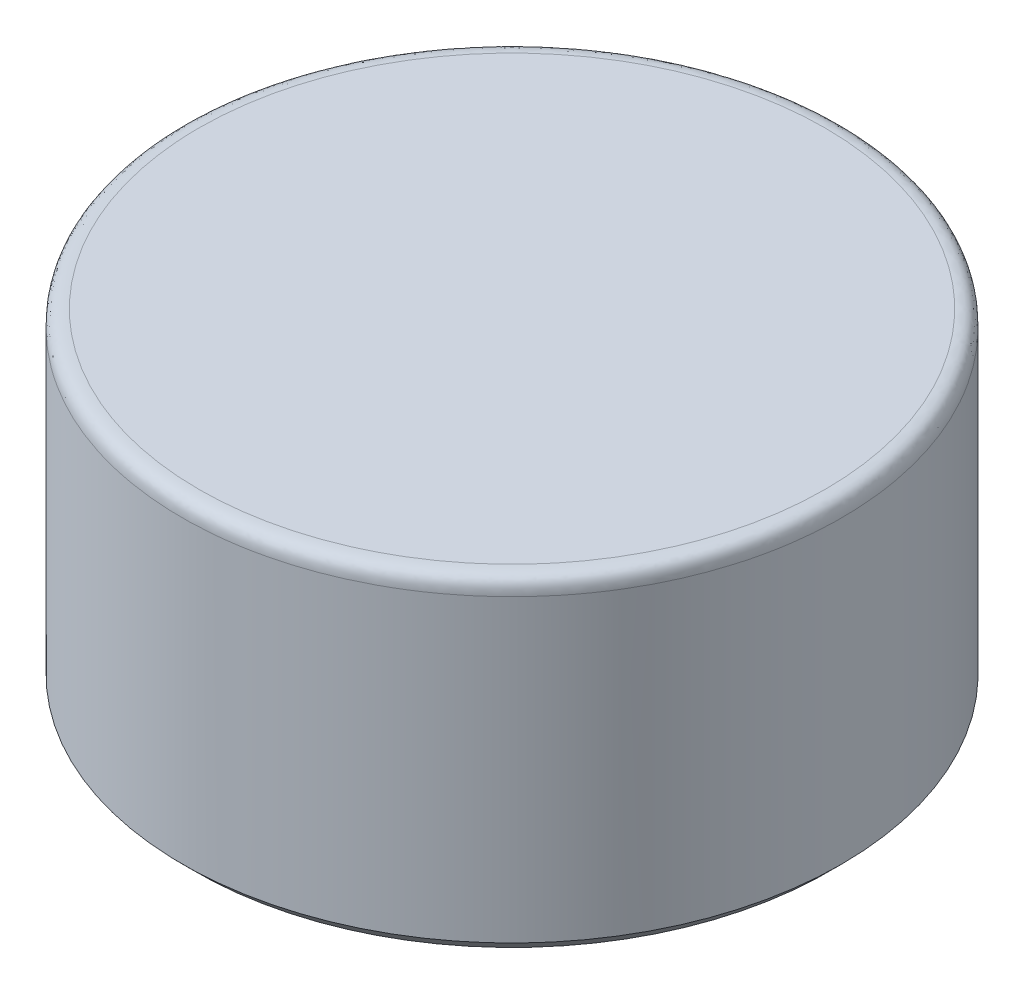
SolidWorks part; units mm, degrees
ref_plane "Front Plane" through (0, 0, 0) normal (0, 0, 1) x (1, 0, 0)
ref_plane "Top Plane" through (0, 0, 0) normal (0, 1, 0) x (1, 0, 0)
ref_plane "Right Plane" through (0, 0, 0) normal (1, 0, 0) x (0, 0, -1)
sketch "Sketch1" plane through (0, 0, 0) normal (0, 0, 1) x (1, 0, 0)
  line L0 (10, 0) -> (10, 10)
  line L1 (10, 10) -> (0, 10)
  line L2 (0, 10) -> (0, 0) construction
  line L3 (9, 0) -> (9, 9)
  line L4 (9, 9) -> (0, 9)
  line L5 (9, 0) -> (10, 0)
  line L6 (0, 10) -> (0, 9)
  dimension "D1" = 9
  dimension "D2" = 10
  dimension "D3" = 1
revolve "Revolve1" add sketch "Sketch1" angle 360 about L6
fillet "Fillet1" radius 0.5 1 edges at (-10, 10, 0) curvature continuous yes
chamfer "Chamfer1" distance 0.4 angle 45 1 edges at (-10, 0, 0)
